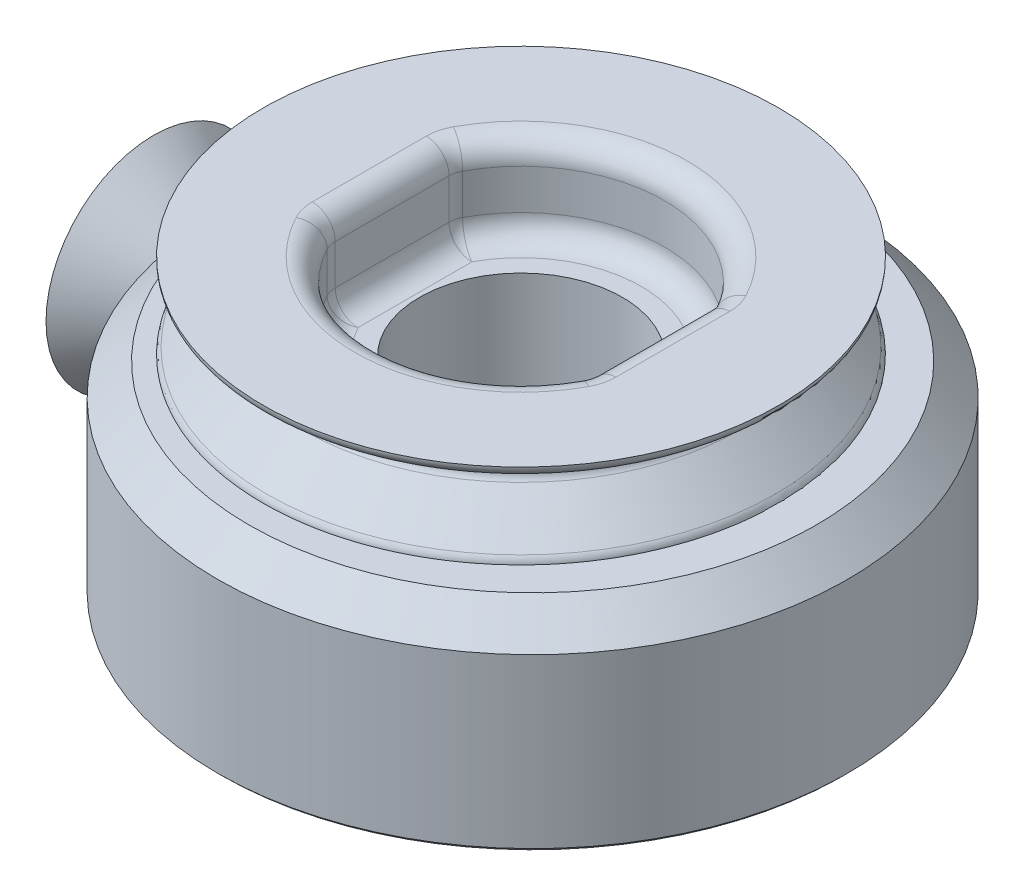
SolidWorks part; units mm, degrees
material "AISI 1020 Steel, Cold Rolled"
ref_plane "Front Plane" through (0, 0, 0) normal (0, 0, 1) x (1, 0, 0)
ref_plane "Top Plane" through (0, 0, 0) normal (0, 1, 0) x (1, 0, 0)
ref_plane "Right Plane" through (0, 0, 0) normal (1, 0, 0) x (0, 0, -1)
other "Center of Mass"
sketch "Sketch1" plane through (0, 0, 0) normal (0, 1, 0) x (1, 0, 0)
  circle A0 centre (0, 0) radius 34.925
  circle A1 centre (0, 0) radius 23.8125
  dimension "D1" = 69.85
  dimension "D2" = 47.625
extrude "Boss-Extrude1" add sketch "Sketch1" along normal mid plane 22.479
chamfer "Chamfer1" distance 2.159 angle 45 2 edges at (0, -11.2395, 23.8125) (0, 11.2395, 23.8125)
chamfer "Chamfer2" distance 3.4798 angle 45 1 edges at (0, 11.2395, 34.925)
chamfer "Chamfer3" distance 0.381 angle 45 1 edges at (0, -11.2395, 34.925)
sketch "Sketch2" plane through (0, 0, 0) normal (0, 1, 0) x (1, 0, 0)
  line L0 (-42.037, 11.9126) -> (-42.037, 0)
  line L1 (-42.037, 0) -> (-17.1196, 0)
  line L2 (-17.1196, 0) -> (-17.1196, 5.3693)
  line L3 (-17.1196, 5.3693) -> (-34.5098, 5.3693)
  line L4 (-34.5098, 5.3693) -> (-42.037, 11.9126)
  circle A0 centre (0, 0) radius 34.925 construction
  point P7 (34.925, 0)
  dimension "D1" = 24.9174
  dimension "D2" = 76.962
  dimension "D3" = 41
  dimension "D4" = 11.9126
revolve "Revolve1" add sketch "Sketch2" angle 360 about L1
other "Center of Mass Reference Point1"
chamfer "Chamfer4" distance 1.27 angle 45 1 edges at (-17.1196, 0, 5.3693)
sketch "Sketch3" plane through (0, 0, 0) normal (0, 1, 0) x (1, 0, 0)
  line L0 (-22.9502, 6.35) -> (-16.4502, 6.35)
  line L1 (-16.4502, 6.35) -> (-16.4502, -6.35)
  line L2 (-16.4502, -6.35) -> (-22.9502, -6.35)
  arc A0 (-22.9502, -6.35) -> (-22.9502, 6.35) centre (0, 0) ccw
  circle A1 centre (0, 0) radius 23.8125 construction
  dimension "D1" = 12.7
  dimension "D2" = 6.5
extrude "Boss-Extrude2" add sketch "Sketch3" along normal mid plane 22.225 separate body
sketch "Sketch4" plane through (0, 11.1125, 0) normal (0, 1, 0) x (1, 0, 0)
  circle A0 centre (-1.2893, 0) radius 11.25
  point P2 (0, 0)
  point P4 (-3.2644, -6.16)
  dimension "D1" = 22.5
  dimension "D2" = 1.2893
extrude "Cut-Extrude1" cut sketch "Sketch4" against normal through all both and the other way through all
ref_axis "Axis1" through (-1.2893, -11.1125, 0) along (0, 1, 0)
fillet "Fillet1" radius 3.302 2 edges at (-16.4502, 0, 6.35) (-16.4502, 0, -6.35)
sketch "Sketch6" plane through (-42.037, 0, 0) normal (-1, 0, 0) x (0, 0, 1)
  line L1 (-4.6194, 0) -> (-2.3097, -4.0005)
  line L2 (-2.3097, -4.0005) -> (2.3097, -4.0005)
  line L3 (2.3097, -4.0005) -> (4.6194, 0)
  line L4 (4.6194, 0) -> (2.3097, 4.0005)
  line L5 (2.3097, 4.0005) -> (-2.3097, 4.0005)
  line L6 (-2.3097, 4.0005) -> (-4.6194, 0)
  circle A0 centre (0, 0) radius 4.0005 construction
  dimension "D1" = 8.001
extrude "Cut-Extrude3" cut sketch "Sketch6" against normal blind 6.35
sketch "Sketch7" plane through (0, 11.1125, 0) normal (0, 1, 0) x (1, 0, 0)
  line L0 (-15.5768, 6.9198) -> (-15.5768, -6.9198)
  line L1 (12.9982, 6.9198) -> (12.9982, -6.9198)
  circle A0 centre (-1.2893, 0) radius 28.575
  arc A1 (12.9982, 6.9198) -> (-15.5768, 6.9198) centre (-1.2893, 0) ccw
  arc A2 (-15.5768, -6.9198) -> (12.9982, -6.9198) centre (-1.2893, 0) ccw
  point P9 (0, 0)
  point P10 (-11.0896, -12.8573)
  dimension "D1" = 57.15
  dimension "D2" = 31.75
  dimension "D3" = 28.575
extrude "Boss-Extrude3" add sketch "Sketch7" along normal blind 9.525
fillet "Fillet2" radius 2.54 12 edges at (12.9982, 20.6375, 0) (12.9982, 11.1125, 0) (12.9982, 15.875, 6.9198) (-1.2893, 20.6375, 15.875) (-1.2893, 11.1125, 15.875) (-15.5768, 15.875, 6.9198) (-15.5768, 20.6375, 0) (-15.5768, 11.1125, 0) (-15.5768, 15.875, -6.9198) (-1.2893, 20.6375, -15.875) (12.9982, 15.875, -6.9198) (-1.2893, 11.1125, -15.875)
sketch "Sketch9" plane through (0, 0, 0) normal (0, 0, 1) x (1, 0, 0)
  line L0 (-49.1154, 15.3453) -> (-37.1526, 15.3453) construction
  line L1 (-37.1526, 15.3453) -> (-37.1526, 18.5203) construction
  line L2 (-37.1526, 18.5203) -> (-52.7445, 18.5203) construction
  line L3 (-29.8643, 20.6375) -> (-29.8643, 11.1125)
  line L4 (-29.1426, 19.537) -> (-25.8309, 18.0975)
  line L5 (-25.4391, 16.0347) -> (-29.5128, 11.961)
  line L7 (-37.1526, 16.9328) -> (-26.3371, 16.9328) construction
  line L8 (27.2857, 20.6375) -> (-29.8643, 20.6375) construction
  line L9 (-1.2893, 9.7331) -> (-1.2893, 23.545) construction
  line L10 (-1.2893, -11.1125) -> (-1.2893, 11.1125) construction
  arc A0 (-29.8643, 20.6375) -> (-29.1426, 19.537) centre (-28.6643, 20.6375) ccw
  arc A1 (-25.8309, 18.0975) -> (-25.4391, 16.0347) centre (-26.3371, 16.9328) cw
  arc A2 (-29.5128, 11.961) -> (-29.8643, 11.1125) centre (-28.6643, 11.1125) ccw
  point P15 (0, 0)
  dimension "D2" = 1.27
  dimension "D4" = 1.2
  dimension "D1" = 3.175
  dimension "D3" = 45
  dimension "D5" = 2.54
revolve "Cut-Revolve1" cut sketch "Sketch9" angle 360 about L9
fillet "Fillet3" radius 0.8 2 edges at (-22.9502, 0, -6.35) (-22.9502, 0, 6.35)
